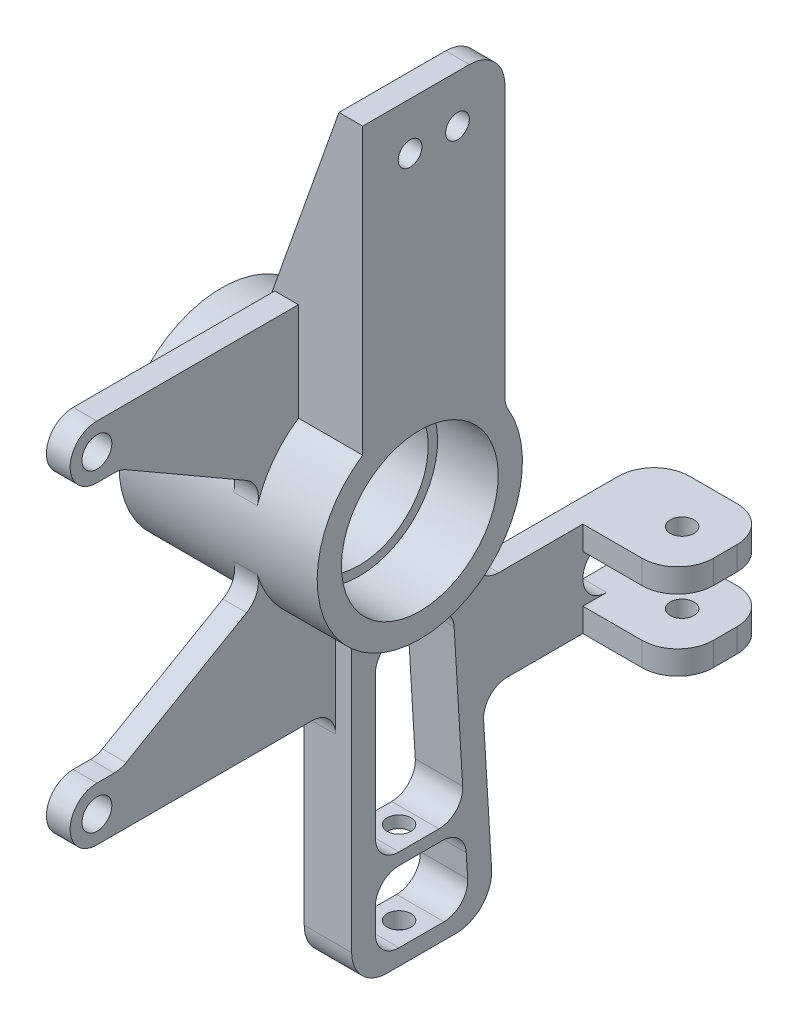
SolidWorks part; units mm, degrees
ref_plane "Front Plane" through (0, 0, 0) normal (0, 0, 1) x (1, 0, 0)
ref_plane "Top Plane" through (0, 0, 0) normal (0, 1, 0) x (1, 0, 0)
ref_plane "Right Plane" through (0, 0, 0) normal (1, 0, 0) x (0, 0, -1)
sketch "Sketch1" plane through (0, 0, 0) normal (0, 0, 1) x (1, 0, 0)
  line L0 (0, 0) -> (53.0908, 0) construction
  line L1 (0, 23.5) -> (16.2791, 23.5)
  line L2 (16.2791, 23.5) -> (16.2791, 18.5)
  line L3 (16.2791, 18.5) -> (36.8482, 18.5)
  line L4 (36.8482, 18.5) -> (36.8482, 21)
  line L5 (36.8482, 21) -> (53.0908, 21)
  line L6 (16.2791, 23.5) -> (16.2791, 0) construction
  line L7 (0, 23.5) -> (0, 0) construction
  line L8 (36.8482, 21) -> (36.8482, 0) construction
  line L9 (53.0908, 21) -> (53.0908, 0) construction
  line L10 (44.9695, 0) -> (61.4795, 0) construction
  line L11 (0, 11.75) -> (16.2791, 11.75) construction
  line L12 (36.8482, 10.5) -> (53.0908, 10.5) construction
  line L13 (0, 23.5) -> (0, 27.5)
  line L14 (0, 27.5) -> (53.0908, 27.5)
  line L15 (53.0908, 27.5) -> (53.0908, 21)
  point P11 (36.8482, 10.5)
  point P19 (8.1395, 11.75)
  point P20 (44.9695, 10.5)
  dimension "D1" = 21
  dimension "D2" = 23.5
  dimension "D3" = 16.2791
  dimension "D4" = 16.2426
  dimension "D5" = 36.83
  dimension "D6" = 4
  dimension "D7" = 2.5
  dimension "D8" = 16.51
revolve "Revolve1" add sketch "Sketch1" angle 360 about L0
sketch "Sketch2" plane through (53.0908, 0, 0) normal (1, 0, 0) x (0, 0, -1)
  line L0 (22.7917, 99.2079) -> (22.7917, 15.3879)
  line L1 (22.7917, 99.2079) -> (-15.3083, 99.2079)
  line L2 (-15.3083, 99.2079) -> (-15.3083, 22.8453)
  line L3 (-1525.5875, -203.2) -> (0, -203.2) construction
  circle A0 centre (0, 0) radius 27.5 construction
  arc A3 (22.7917, 15.3879) -> (-15.3083, 22.8453) centre (0, 0) ccw
  point P8 (3.7417, 99.2079)
  dimension "D1" = 83.82
  dimension "D2" = 38.1
extrude "Boss-Extrude1" add sketch "Sketch2" against normal blind 6.35
ref_plane "Plane1" through (33.8016, 0, 0) normal (1, 0, 0) x (0, 0, -1)
sketch "Sketch4" plane through (33.8016, 0, 0) normal (1, 0, 0) x (0, 0, -1)
  line L3 (0, 0) -> (13.7254, -101.6) construction
  line L4 (26.4254, -7.6125) -> (32.7754, -113.538)
  line L10 (-5.3246, -26.9796) -> (-5.3246, -113.538)
  line L15 (-5.3246, -113.538) -> (32.7754, -113.538)
  circle A0 centre (0, 0) radius 27.5 construction
  arc A1 (-5.3246, -26.9796) -> (26.4254, -7.6125) centre (0, 0) ccw
  point P3 (13.7254, -113.538)
  dimension "D1" = 11.938
  dimension "D2" = 38.1
  dimension "D7" = 31.75
extrude "Boss-Extrude2" add sketch "Sketch4" against normal blind 6.35 and the other way blind 6.35
sketch "Sketch5" plane through (40.1516, 0, 0) normal (1, 0, 0) x (0, 0, -1)
  line L0 (29.6234, -60.96) -> (82.0236, -60.96)
  line L2 (82.0236, -60.96) -> (82.0236, -54.61)
  line L3 (82.0236, -54.61) -> (56.6236, -54.61)
  line L4 (56.6236, -54.61) -> (56.6236, -41.91)
  line L5 (56.6236, -41.91) -> (82.0236, -41.91)
  line L6 (82.0236, -41.91) -> (82.0236, -35.56)
  line L7 (82.0236, -35.56) -> (28.1008, -35.56)
  line L9 (32.7754, -113.538) -> (26.4254, -7.6125) construction
  line L10 (28.1008, -35.56) -> (29.6234, -60.96)
  point P2 (69.3236, -54.61)
  point P10 (56.6236, -48.26)
  dimension "D1" = 6.35
  dimension "D2" = 25.4
  dimension "D3" = 12.7
extrude "Boss-Extrude3" add sketch "Sketch5" against normal blind 6.35
sketch "Sketch6" plane through (40.1516, 0, 0) normal (1, 0, 0) x (0, 0, -1)
  line L0 (82.0236, -54.61) -> (56.6236, -54.61) construction
  line L1 (82.0236, -35.56) -> (56.6236, -35.56)
  line L2 (82.0236, -35.56) -> (82.0236, -41.91)
  line L3 (82.0236, -41.91) -> (56.6236, -41.91)
  line L4 (56.6236, -35.56) -> (56.6236, -41.91)
  line L5 (82.0236, -60.96) -> (56.6236, -60.96)
  line L6 (82.0236, -60.96) -> (82.0236, -54.61)
  line L7 (82.0236, -54.61) -> (56.6236, -54.61)
  line L8 (56.6236, -60.96) -> (56.6236, -54.61)
  line L9 (56.6236, -54.61) -> (56.6236, -41.91) construction
extrude "Boss-Extrude4" add sketch "Sketch6" along normal blind 25.4
sketch "Sketch7" plane through (46.7408, 0, 0) normal (-1, 0, 0) x (0, 0, 1)
  line L0 (15.3083, 22.8453) -> (15.3083, 99.2079)
  line L1 (15.3083, 99.2079) -> (15.3083, 22.8453) construction
  line L2 (15.3083, 99.2079) -> (8.9583, 99.2079)
  line L3 (8.9583, 99.2079) -> (8.9583, 26)
  line L4 (-22.7917, 99.2079) -> (15.3083, 99.2079) construction
  circle A0 centre (0, 0) radius 27.5 construction
  arc A1 (15.3083, 22.8453) -> (-22.7917, 15.3879) centre (0, 0) ccw construction
  arc A2 (15.3083, 22.8453) -> (8.9583, 26) centre (0, 0) ccw
  dimension "D1" = 6.35
extrude "Boss-Extrude5" add sketch "Sketch7" along normal blind 25.4
sketch "Sketch8" plane through (35.8795, 0, 0) normal (-1, 0, 0) x (0, 0, 1)
  line L0 (15.3083, 22.8453) -> (15.3083, 99.2079) construction
  line L1 (15.3083, 49.175) -> (69.3, 49.175)
  line L4 (15.3083, 22.8453) -> (15.3083, 49.175)
  line L7 (24.4463, 12.5949) -> (62.95, 34.825)
  line L8 (62.95, 34.825) -> (69.3, 34.825)
  arc A0 (69.3, 38) -> (69.3, 46) centre (69.3, 42) ccw construction
  arc A1 (69.3, 46) -> (69.3, 38) centre (69.3, 42) ccw construction
  arc A2 (69.3, 38) -> (69.3, 46) centre (69.3, 42) ccw
  arc A3 (69.3, 46) -> (69.3, 38) centre (69.3, 42) ccw
  circle A4 centre (0, 0) radius 27.5 construction
  arc A6 (69.3, 34.825) -> (69.3, 49.175) centre (69.3, 42) ccw
  arc A14 (24.4463, 12.5949) -> (15.3083, 22.8453) centre (0, 0) ccw
  dimension "D1" = 3.175
  dimension "D2" = 30
  dimension "D3" = 6.35
extrude "Boss-Extrude6" add sketch "Sketch8" along normal blind 6.35
sketch "Sketch9" plane through (35.8795, 0, 0) normal (-1, 0, 0) x (0, 0, 1)
  line L0 (5.3246, -49.175) -> (69.3, -49.175)
  line L1 (5.3246, -26.9796) -> (5.3246, -113.538) construction
  line L3 (5.3246, -49.175) -> (5.3246, -26.9796)
  line L5 (69.3, -34.825) -> (62.95, -34.825)
  line L6 (62.95, -34.825) -> (24.4463, -12.5949)
  arc A0 (69.3, -46) -> (69.3, -38) centre (69.3, -42) ccw construction
  arc A1 (69.3, -38) -> (69.3, -46) centre (69.3, -42) ccw construction
  arc A2 (69.3, -46) -> (69.3, -38) centre (69.3, -42) ccw
  arc A3 (69.3, -38) -> (69.3, -46) centre (69.3, -42) ccw
  arc A4 (69.3, -49.175) -> (69.3, -34.825) centre (69.3, -42) ccw
  circle A5 centre (0, 0) radius 27.5 construction
  arc A7 (5.3246, -26.9796) -> (24.4463, -12.5949) centre (0, 0) ccw
  dimension "D1" = 3.175
  dimension "D3" = 6.35
  dimension "D2" = 30
extrude "Boss-Extrude7" add sketch "Sketch9" along normal blind 6.35
sketch "Sketch10" plane through (0, 0, 8.9583) normal (0, 0, -1) x (-1, 0, 0)
  line L0 (-46.7408, 99.2079) -> (-21.3408, 27.5)
  line L1 (-21.3408, 99.2079) -> (-21.3408, 26) construction
  line L2 (-21.3408, 27.5) -> (-21.3408, 99.2079)
  line L3 (-21.3408, 99.2079) -> (-46.7408, 99.2079)
  line L4 (0, 27.5) -> (-53.0908, 27.5) construction
extrude "Cut-Extrude1" cut sketch "Sketch10" against normal up to next
sketch "Sketch13" plane through (40.1516, 0, 0) normal (1, 0, 0) x (0, 0, -1)
  line L0 (26.1551, -109.22) -> (25.0131, -90.17)
  line L1 (25.0131, -90.17) -> (1.0254, -90.17)
  line L2 (1.0254, -90.17) -> (1.0254, -109.22)
  line L3 (1.0254, -109.22) -> (26.1551, -109.22)
  line L4 (21.7774, -36.195) -> (24.8228, -86.995)
  line L5 (24.8228, -86.995) -> (1.0254, -86.995)
  line L6 (1.0254, -86.995) -> (1.0254, -36.195)
  line L7 (1.0254, -36.195) -> (21.7774, -36.195)
  line L8 (32.7754, -113.538) -> (29.6234, -60.96) construction
  line L9 (-5.3246, -26.9796) -> (-5.3246, -113.538) construction
  point P12 (11.6399, -100.7497)
  point P16 (0, 0)
  point P17 (13.4014, -101.7447)
  point P20 (0, 0)
  dimension "D1" = 6.35
  dimension "D2" = 6.35
  dimension "D3" = 3.175
  dimension "D4" = 7.62
  dimension "D5" = 19.05
  dimension "D6" = 50.8
extrude "Cut-Extrude2" cut sketch "Sketch13" against normal up to next
sketch "Sketch14" plane through (0, -86.995, 0) normal (0, 1, 0) x (1, 0, 0)
  circle A0 centre (33.8016, 13.7254) radius 3.175
  dimension "D1" = 6.35
extrude "Cut-Extrude3" cut sketch "Sketch14" against normal through all
sketch "Sketch15" plane through (53.0908, 0, 0) normal (1, 0, 0) x (0, 0, -1)
  line L0 (-2.6083, 86.5079) -> (10.0917, 86.5079) construction
  line L1 (22.7917, 99.2079) -> (-15.3083, 99.2079) construction
  circle A0 centre (-2.6083, 86.5079) radius 3.175
  circle A1 centre (10.0917, 86.5079) radius 3.175
  point P6 (3.7417, 99.2079)
  point P7 (3.7417, 86.5079)
  point P8 (-5.3573, 86.5079)
  dimension "D1" = 6.35
  dimension "D3" = 12.7
  dimension "D2" = 12.7
extrude "Cut-Extrude4" cut sketch "Sketch15" against normal up to next
sketch "Sketch16" plane through (0, -35.56, 0) normal (0, 1, 0) x (1, 0, 0)
  circle A0 centre (54.033, 69.3236) radius 3.175
  dimension "D1" = 6.35
extrude "Cut-Extrude5" cut sketch "Sketch16" against normal through all
fillet "0.25 Fillet4" radius 6.35 22 edges at (32.7045, -34.825, 62.95) (32.7045, 34.825, 62.95) (25.4352, 22.8453, 15.3083) (36.9766, -54.61, -56.6236) (36.9766, -41.91, -56.6236) (33.8016, -109.22, -1.0254) (33.8016, -109.22, -26.1551) (33.8016, -90.17, -1.0254) (33.8016, -90.17, -25.0131) (33.8016, -86.995, -1.0254) (33.8016, -86.995, -24.8228) (33.8016, -7.6125, -26.4254) (33.8016, -36.195, -1.0254) (33.8016, -36.195, -21.7774) (36.9766, -60.96, -29.6234) (36.9766, -35.56, -28.1008) (32.7045, -49.175, 5.3246) (32.7045, -12.5949, 24.4463) (32.7045, 12.5949, 24.4463) (34.0408, 26, 8.9583) (49.9158, 15.3879, -22.7917) (38.0156, -26.9796, 5.3246)
fillet "Fillet1" radius 9.525 9 edges at (33.8016, -113.538, 5.3246) (33.8016, -113.538, -32.7754) (49.9158, 99.2079, -22.7917) (65.5516, -57.785, -82.0236) (65.5516, -57.785, -56.6236) (65.5516, -38.735, -56.6236) (65.5516, -38.735, -82.0236) (33.8016, -57.785, -82.0236) (33.8016, -38.735, -82.0236)
